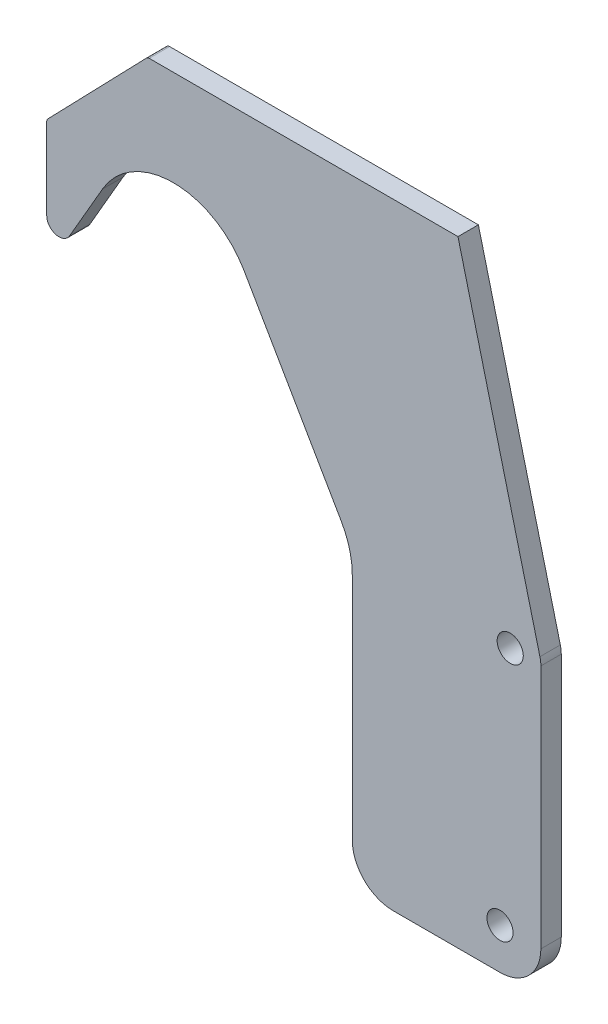
SolidWorks part; units mm, degrees
ref_plane "Front Plane" through (0, 0, 0) normal (0, 0, 1) x (1, 0, 0)
ref_plane "Top Plane" through (0, 0, 0) normal (0, 1, 0) x (1, 0, 0)
ref_plane "Right Plane" through (0, 0, 0) normal (1, 0, 0) x (0, 0, -1)
sketch "Sketch1" plane through (0, 0, 0) normal (0, 0, 1) x (1, 0, 0)
  line L0 (-10.9985, 23.8125) -> (-26.1215, -2.3812) construction
  line L1 (-15.123, -21.4313) -> (15.123, -21.4313) construction
  line L2 (26.1215, -2.3812) -> (10.9985, 23.8125) construction
  line L3 (10.9985, 23.8125) -> (26.1215, -2.3812)
  line L4 (-10.9985, 23.8125) -> (-16.1312, 14.9225)
  line L5 (-19.6859, 15.875) -> (-19.6859, 28.575)
  line L6 (-19.5249, 28.9732) -> (-4.1728, 44.8482)
  line L8 (57.15, -6.35) -> (57.15, -44.45)
  line L9 (50.8, -50.8) -> (34.173, -50.8)
  line L13 (27.823, -8.7312) -> (27.823, -44.45)
  line L14 (-3.761, 45.0229) -> (44.2584, 45.0229)
  line L15 (57.0036, -5.1781) -> (44.2584, 45.0229)
  circle A0 centre (0, 0) radius 21.4313 construction
  arc A1 (10.9985, 23.8125) -> (-10.9985, 23.8125) centre (0, 17.4625) ccw construction
  arc A2 (-26.1215, -2.3812) -> (-15.123, -21.4313) centre (-15.123, -8.7313) ccw construction
  arc A3 (15.123, -21.4313) -> (26.1215, -2.3812) centre (15.123, -8.7312) ccw construction
  arc A4 (-10.9985, 23.8125) -> (10.9985, 23.8125) centre (0, 17.4625) cw
  arc A5 (26.1215, -2.3812) -> (27.823, -8.7312) centre (15.123, -8.7312) cw
  arc A6 (57.15, -6.35) -> (57.0036, -5.1781) centre (52.3875, -6.35) ccw
  arc A7 (-3.761, 45.0229) -> (-4.1728, 44.8482) centre (-3.761, 44.45) ccw
  arc A8 (-19.5249, 28.9732) -> (-19.6859, 28.575) centre (-19.1131, 28.575) ccw
  arc A9 (-19.6859, 15.875) -> (-16.1312, 14.9225) centre (-17.7809, 15.875) ccw
  arc A10 (50.8, -50.8) -> (57.15, -44.45) centre (50.8, -44.45) ccw
  arc A11 (27.823, -44.45) -> (34.173, -50.8) centre (34.173, -44.45) ccw
  circle A12 centre (50.8, -44.45) radius 2.032
  circle A15 centre (52.3875, -6.35) radius 2.032
  point P35 (24.7277, 45.4716)
  point P36 (0, 0)
  point P37 (-3.761, 44.45)
  point P39 (37.3728, 44.45)
  point P40 (44.3471, 44.45)
  dimension "D2" = 12.7
  dimension "D3" = 9.525
  dimension "D1" = 42.8625
  dimension "D4" = 30
  dimension "D5" = 1.905
  dimension "D12" = 4.064
  dimension "D9" = 50.8
  dimension "D6" = 12.7
  dimension "D7" = 44.45
  dimension "D8" = 15.875
  dimension "D14" = 50.8
  dimension "D15" = 44.45
  dimension "D16" = 38.1
extrude "Boss-Extrude1" add sketch "Sketch1" along normal mid plane 3.175
